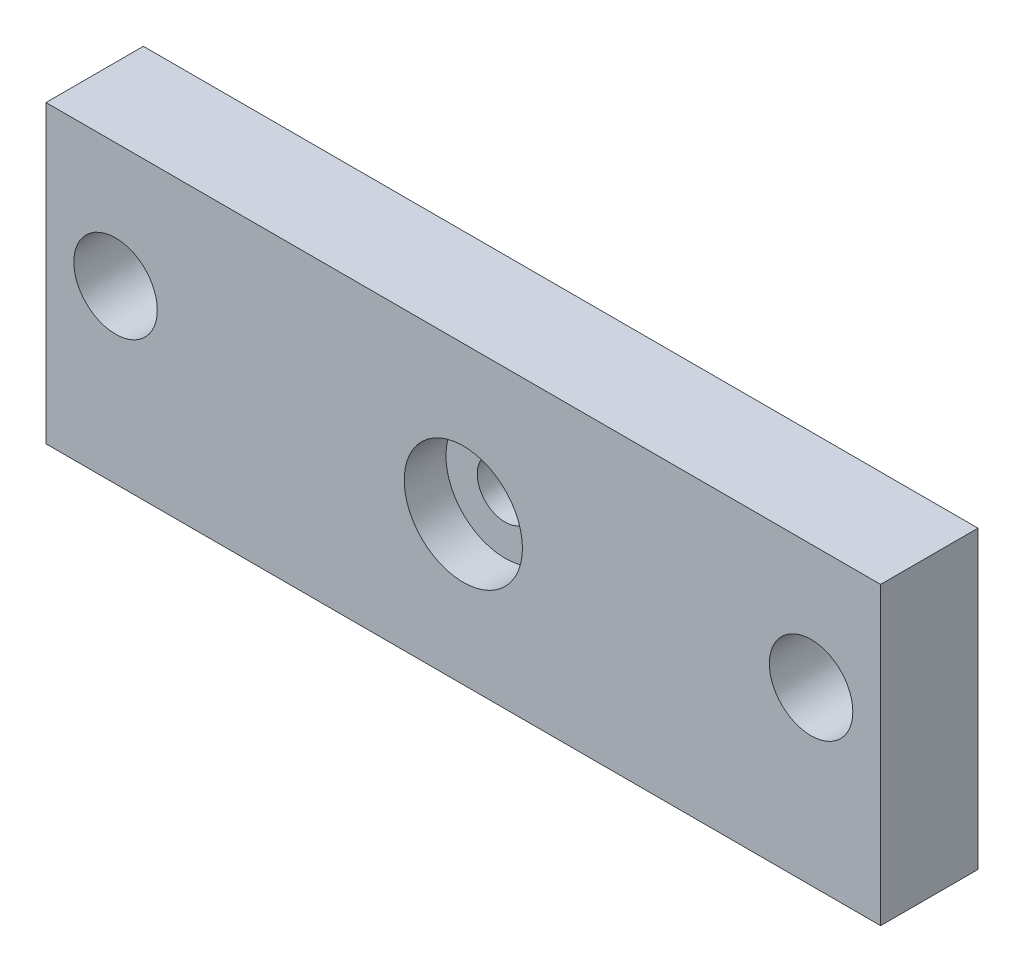
SolidWorks part; units mm, degrees
ref_plane "Front Plane" through (0, 0, 0) normal (0, 0, 1) x (1, 0, 0)
ref_plane "Top Plane" through (0, 0, 0) normal (0, 1, 0) x (1, 0, 0)
ref_plane "Right Plane" through (0, 0, 0) normal (1, 0, 0) x (0, 0, -1)
sketch "Sketch1" plane through (0, 0, 0) normal (0, 0, 1) x (1, 0, 0)
  line L1 (-60, -21.25) -> (60, -21.25)
  line L2 (-60, -21.25) -> (-60, 21.25)
  line L3 (-60, 21.25) -> (60, 21.25)
  line L4 (60, -21.25) -> (60, 21.25)
  line L5 (-60, -21.25) -> (60, 21.25) construction
  line L6 (-60, 21.25) -> (60, -21.25) construction
  point P0 (0, 0)
  dimension "D1" = 120
  dimension "D2" = 42.5
extrude "Boss-Extrude1" add sketch "Sketch1" along normal mid plane 14
sketch "Sketch2" plane through (0, 0, 7) normal (0, 0, 1) x (1, 0, 0)
  circle A0 centre (0, 0) radius 8.5
  dimension "D1" = 17
extrude "Cut-Extrude1" cut sketch "Sketch2" against normal blind 6
sketch "Sketch3" plane through (0, 0, 1) normal (0, 0, 1) x (1, 0, 0)
  circle A0 centre (0, 0) radius 4
  dimension "D1" = 8
extrude "Cut-Extrude2" cut sketch "Sketch3" against normal through all
sketch "Sketch5" plane through (0, 0, 7) normal (0, 0, 1) x (1, 0, 0)
  line L0 (-40.6477, 3.4) -> (36.4799, 3.4) construction
  circle A0 centre (-50, 3.4) radius 6
  circle A1 centre (50, 3.4) radius 6
  dimension "D1" = 12
  dimension "D2" = 12
  dimension "D4" = 50
  dimension "D3" = 50
  dimension "D5" = 3.4
extrude "Cut-Extrude4" cut sketch "Sketch5" against normal through all
sketch "Sketch6" plane through (0, -21.25, 0) normal (0, -1, 0) x (1, 0, 0)
  line L0 (-60, 0) -> (60, 0) construction
  line L1 (-60, 7) -> (-60, -7) construction
  line L2 (60, 7) -> (60, -7) construction
  circle A0 centre (-50, 0) radius 2.1
  circle A1 centre (-25, 0) radius 2.1
  circle A2 centre (25, 0) radius 2.1
  circle A3 centre (50, 0) radius 2.1
  circle A4 centre (-37.5, 0) radius 1.25
  circle A5 centre (37.5, 0) radius 1.25
  dimension "D1" = 4.2
  dimension "D2" = 4.2
  dimension "D3" = 4.2
  dimension "D4" = 4.2
  dimension "D5" = 10
  dimension "D9" = 2.5
  dimension "D10" = 2.5
  dimension "D11" = 22.5
  dimension "D12" = 22.5
  dimension "D6" = 35
  dimension "D7" = 10
  dimension "D8" = 35
extrude "Cut-Extrude5" cut sketch "Sketch6" against normal blind 10
